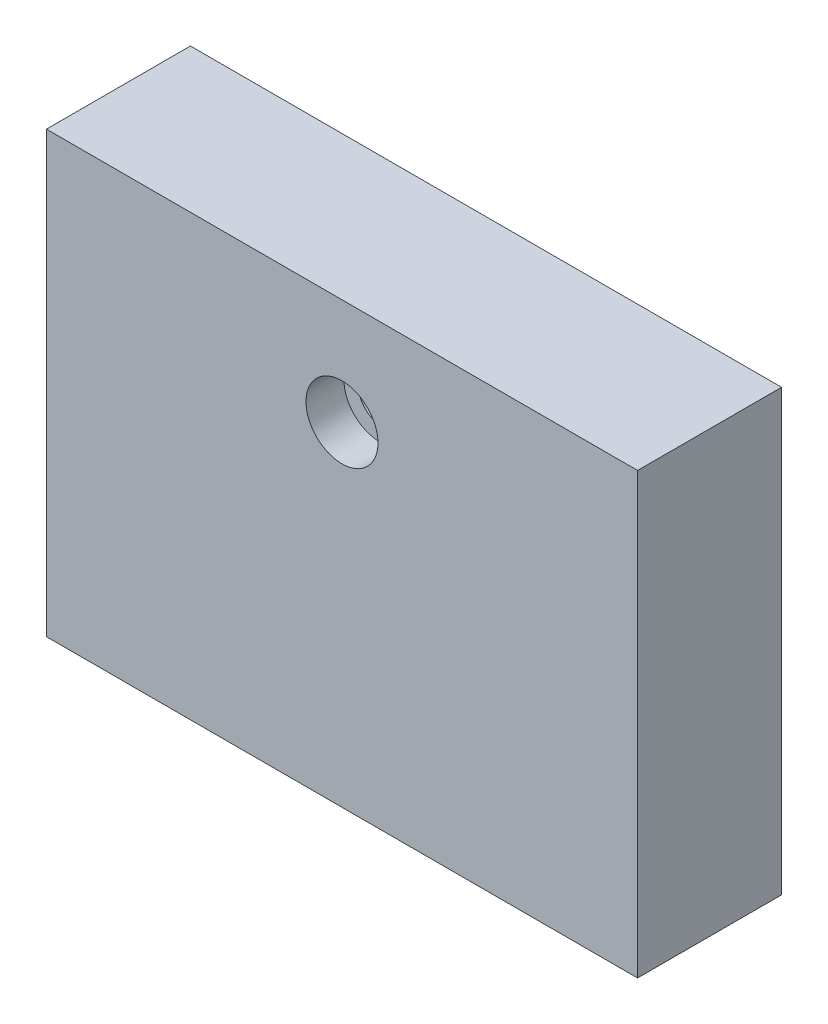
SolidWorks part; units mm, degrees
ref_plane "Piano frontale" through (0, 0, 0) normal (0, 0, 1) x (1, 0, 0)
ref_plane "Piano superiore" through (0, 0, 0) normal (0, 1, 0) x (1, 0, 0)
ref_plane "Piano destro" through (0, 0, 0) normal (1, 0, 0) x (0, 0, -1)
sketch "Sketch1" plane through (0, 0, 0) normal (0, 0, 1) x (1, 0, 0)
  line L1 (0, 0) -> (78, 0)
  line L2 (0, 0) -> (0, 58)
  line L3 (0, 58) -> (78, 58)
  line L4 (78, 0) -> (78, 58)
  dimension "D1" = 58
  dimension "D2" = 78
extrude "Boss-Extrude1" add sketch "Sketch1" along normal blind 19
sketch "Sketch2" plane through (0, 0, 19) normal (0, 0, 1) x (1, 0, 0)
  line L0 (78, 0) -> (78, 58) construction
  line L1 (0, 0) -> (78, 0) construction
  line L2 (0, 58) -> (0, 0) construction
  line L3 (78, 58) -> (0, 58) construction
  line L4 (78, 0) -> (78, 58)
  line L5 (0, 0) -> (78, 0)
  line L6 (0, 58) -> (0, 0)
  line L7 (78, 58) -> (0, 58)
  circle A0 centre (39, 44) radius 4.75
  circle A1 centre (39, 44) radius 2.75
  dimension "D1" = 9.5
  dimension "D2" = 5.5
  dimension "D3" = 39
  dimension "D4" = 14
extrude "Cut-Extrude1" cut sketch "Sketch2" against normal blind 5 contours A0
extrude "Cut-Extrude2" cut sketch "Sketch2<3>" against normal through all from surface contours A1 starting at face at (43.75, 44, 14)
sketch "Sketch2<3>" plane through (0, 0, 19) normal (0, 0, 1) x (1, 0, 0) same geometry as "Sketch2"
